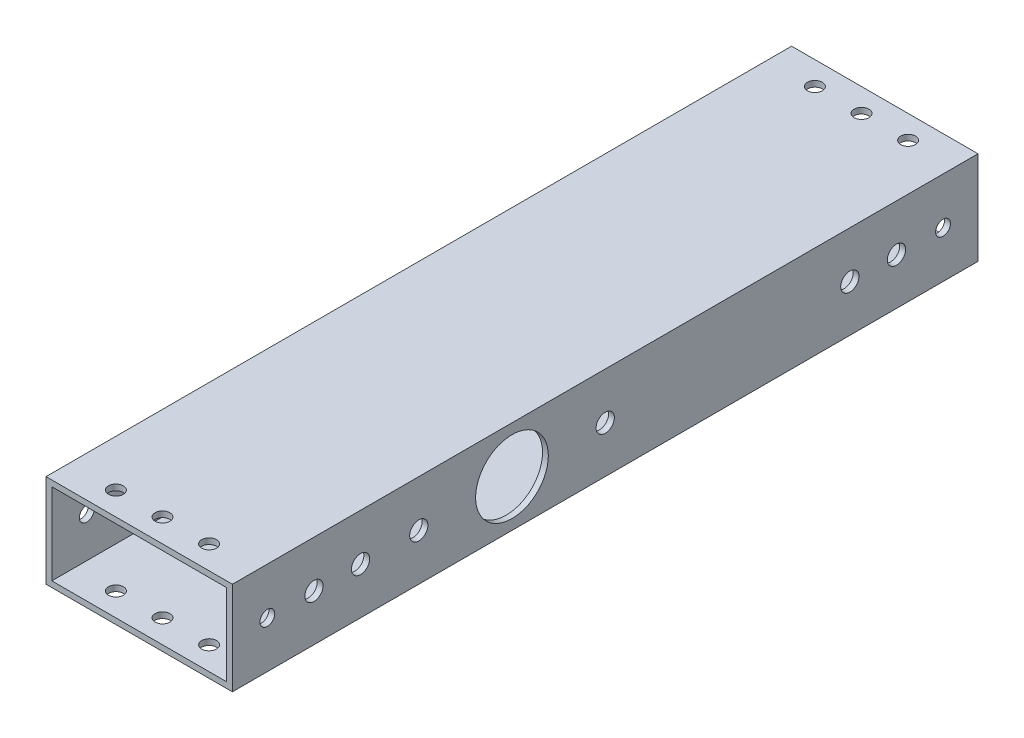
SolidWorks part; units mm, degrees
material "6061-T6 (SS)"
ref_plane "Front Plane" through (0, 0, 0) normal (0, 0, 1) x (1, 0, 0)
ref_plane "Top Plane" through (0, 0, 0) normal (0, 1, 0) x (1, 0, 0)
ref_plane "Right Plane" through (0, 0, 0) normal (1, 0, 0) x (0, 0, -1)
sketch "Sketch1" plane through (0, 0, 0) normal (0, 0, 1) x (1, 0, 0)
  line L0 (-23.8125, 11.1125) -> (23.8125, 11.1125)
  line L1 (-25.4, -12.7) -> (25.4, -12.7)
  line L2 (-25.4, -12.7) -> (-25.4, 12.7)
  line L3 (-25.4, 12.7) -> (25.4, 12.7)
  line L4 (25.4, -12.7) -> (25.4, 12.7)
  line L5 (-25.4, -12.7) -> (25.4, 12.7) construction
  line L6 (-25.4, 12.7) -> (25.4, -12.7) construction
  line L7 (23.8125, -11.1125) -> (23.8125, 11.1125)
  line L8 (-23.8125, -11.1125) -> (23.8125, -11.1125)
  line L9 (-23.8125, -11.1125) -> (-23.8125, 11.1125)
  point P0 (0, 0)
  dimension "D1" = 50.8
  dimension "D2" = 25.4
  dimension "D3" = 1.5875
extrude "Boss-Extrude1" add sketch "Sketch1" along normal mid plane 203.2
sketch "Sketch2" plane through (25.4, 0, 0) normal (1, 0, 0) x (0, 0, -1)
  line L0 (-101.6, -12.7) -> (-101.6, 12.7) construction
  line L1 (0, 12.7) -> (0, -12.7) construction
  line L2 (-101.6, 12.7) -> (101.6, 12.7) construction
  line L3 (-101.6, -12.7) -> (101.6, -12.7) construction
  circle A0 centre (-92.075, 0) radius 2.0193
  circle A1 centre (92.075, 0) radius 2.0193
  circle A2 centre (-79.375, 0) radius 2.4892
  circle A3 centre (-66.675, 0) radius 2.4892
  circle A4 centre (66.675, 0) radius 2.4892
  circle A5 centre (79.375, 0) radius 2.4892
  dimension "D2" = 4.0386
  dimension "D5" = 4.9784
  dimension "D1" = 9.525
  dimension "D3" = 12.7
  dimension "D4" = 12.7
extrude "Cut-Extrude1" cut sketch "Sketch2" against normal through all
sketch "Sketch3" plane through (0, 12.7, 0) normal (0, 1, 0) x (1, 0, 0)
  line L0 (-25.4, 0) -> (25.4, 0) construction
  line L1 (-25.4, -101.6) -> (-25.4, 101.6) construction
  line L2 (25.4, -101.6) -> (25.4, 101.6) construction
  line L3 (25.4, -101.6) -> (-25.4, -101.6) construction
  circle A0 centre (-12.7, -95.25) radius 2.0193
  circle A1 centre (0, -95.25) radius 2.0193
  circle A2 centre (12.7, -95.25) radius 2.0193
  circle A3 centre (12.7, 95.25) radius 2.0193
  circle A4 centre (0, 95.25) radius 2.0193
  circle A5 centre (-12.7, 95.25) radius 2.0193
  dimension "D1" = 4.0386
  dimension "D2" = 12.7
  dimension "D3" = 12.7
  dimension "D4" = 6.35
extrude "Cut-Extrude2" cut sketch "Sketch3" against normal through all
sketch "Sketch4" plane through (25.4, 0, 0) normal (1, 0, 0) x (0, 0, -1)
  line L1 (0, 0) -> (-50.8, 0) construction
  line L7 (101.6, -12.7) -> (101.6, 12.7) construction
  circle A0 centre (-25.4, 0) radius 9.906
  circle A5 centre (-50.8, 0) radius 2.4892
  circle A6 centre (0, 0) radius 2.4892
  point P7 (-25.4, 0)
  point P10 (0, 0)
  dimension "D2" = 19.812
  dimension "D3" = 25.4
  dimension ".196" = 4.9784
  dimension "5" = 127
extrude "Cut-Extrude3" cut sketch "Sketch4" against normal through all contours A0 | A5 | A6
